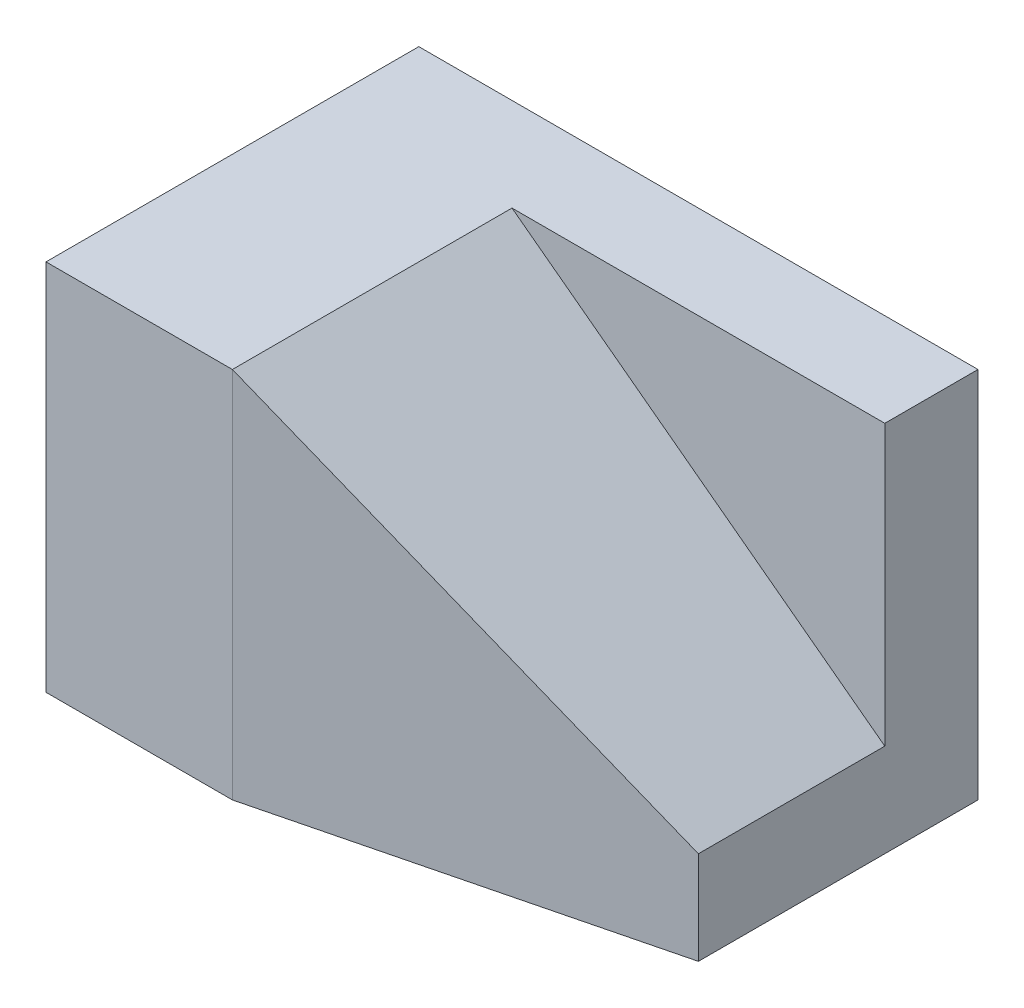
SolidWorks part; units mm, degrees
ref_plane "前基準面" through (0, 0, 0) normal (0, 0, 1) x (1, 0, 0)
ref_plane "上基準面" through (0, 0, 0) normal (0, 1, 0) x (1, 0, 0)
ref_plane "右基準面" through (0, 0, 0) normal (1, 0, 0) x (0, 0, -1)
sketch "草圖1" plane through (0, 0, 0) normal (0, 1, 0) x (1, 0, 0)
  line L0 (-5, -10) -> (15, -5)
  line L1 (15, 10) -> (-15, 10)
  line L2 (15, 10) -> (15, -5)
  line L3 (-5, -10) -> (-15, -10)
  line L4 (-15, 10) -> (-15, -10)
  line L5 (15, 10) -> (-15, -10) construction
  line L6 (9.5455, -6.3636) -> (-15, 10) construction
  line L8 (15, -5) -> (15, 5)
  line L9 (15, 5) -> (-5, 5)
  line L10 (-5, -10) -> (-5, 5)
  point P0 (0, 0)
  dimension "D1" = 20
  dimension "D2" = 30
  dimension "D3" = 5
  dimension "D4" = 10
extrude "填料-伸長1" add sketch "草圖1" along normal blind 20 contours L10 L0 L2 L9 region at (4.3333, 0, 1.3333)
extrude "填料-伸長2" add sketch "草圖1<3>" along normal blind 20 contours L3 L10 L9 L2 L1 L4 region at (-10, 0, 9.6394)
sketch "草圖1<3>" plane through (0, 0, 0) normal (0, 1, 0) x (1, 0, 0) same geometry as "草圖1"
sketch "草圖2" plane through (0, 0, 10) normal (0, 0, 1) x (1, 0, 0)
  line L0 (-5, 20) -> (15, 5)
  line L1 (15, 20) -> (15, 0) construction
  line L2 (15, 5) -> (15, 20)
  line L3 (15, 20) -> (-5, 20)
  dimension "D1" = 15
extrude "除料-伸長1" cut sketch "草圖2" against normal blind 15
